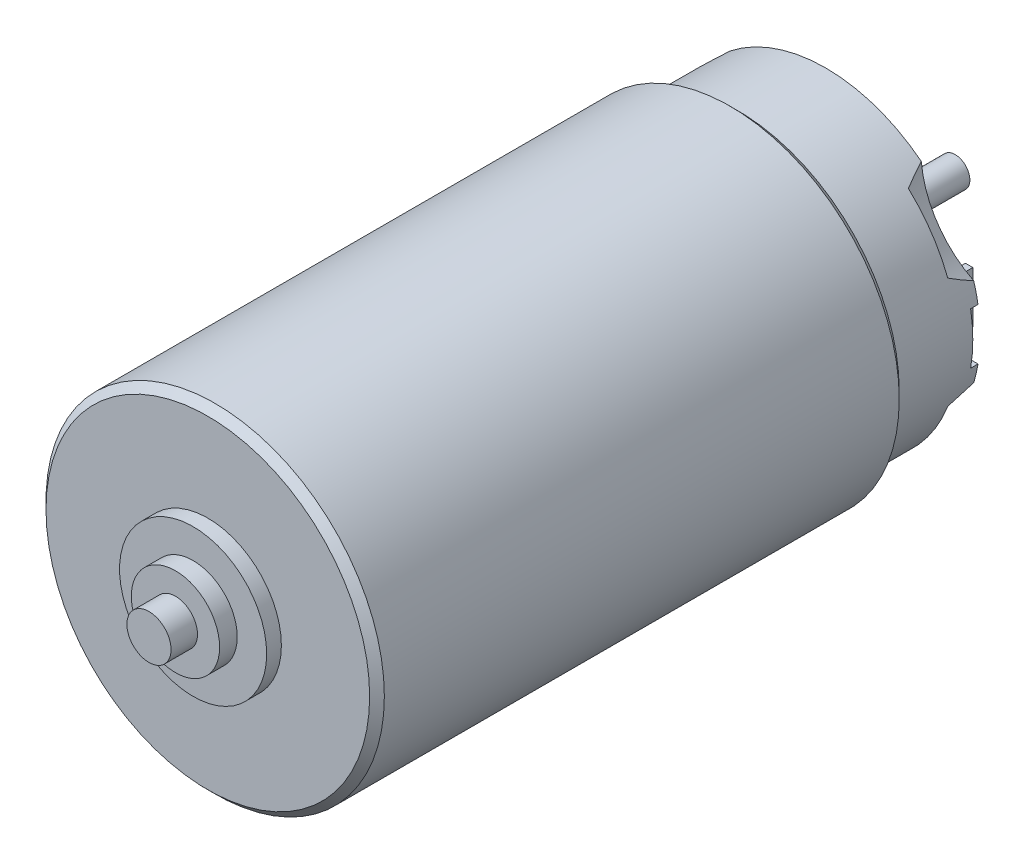
SolidWorks part; units mm, degrees
note: The reader was unsure of these and kept them because the rebuilt part matched: shared geometry of "Croquis1<4>", "Croquis1<5>", "Croquis1<6>", "Croquis3<6>", "Croquis3<8>", "Croquis3<9>".
ref_plane "Alzado" through (0, 0, 0) normal (0, 0, 1) x (1, 0, 0)
ref_plane "Planta" through (0, 0, 0) normal (0, 1, 0) x (1, 0, 0)
ref_plane "Vista lateral" through (0, 0, 0) normal (1, 0, 0) x (0, 0, -1)
sketch "Croquis1" plane through (0, 0, 0) normal (0, 0, 1) x (1, 0, 0)
  circle A0 centre (0, 0) radius 11.5
  circle A1 centre (0, 0) radius 5
  circle A2 centre (0, 0) radius 3
  circle A3 centre (0, 0) radius 1.5
  dimension "D1" = 23
  dimension "D2" = 10
  dimension "D3" = 6
  dimension "D4" = 3
extrude "Saliente-Extruir1" add sketch "Croquis1" against normal blind 36 contours A0
extrude "Saliente-Extruir2" add sketch "Croquis1<4>" along normal blind 1 contours A1
sketch "Croquis1<4>" plane through (0, 0, 0) normal (0, 0, 1) x (1, 0, 0) same geometry as "Croquis1"
extrude "Saliente-Extruir3" add sketch "Croquis1<5>" along normal blind 2.2 contours A2
sketch "Croquis1<5>" plane through (0, 0, 0) normal (0, 0, 1) x (1, 0, 0) same geometry as "Croquis1"
extrude "Saliente-Extruir4" add sketch "Croquis1<6>" along normal blind 4 contours A3
sketch "Croquis1<6>" plane through (0, 0, 0) normal (0, 0, 1) x (1, 0, 0) same geometry as "Croquis1"
sketch "Croquis3" plane through (0, 0, -36) normal (0, 0, -1) x (-1, 0, 0)
  circle A0 centre (0, 0) radius 10.5
  circle A1 centre (0, 0) radius 4.5
  circle A2 centre (0, 0) radius 3
  circle A3 centre (0, 0) radius 1
  dimension "D1" = 21
  dimension "D2" = 9
  dimension "D3" = 6
  dimension "D4" = 2
extrude "Saliente-Extruir5" add sketch "Croquis3" along normal blind 5 contours A0
sketch "Croquis7" plane through (0, 0, -41) normal (0, 0, -1) x (-1, 0, 0)
  circle A0 centre (0, 0) radius 10.5
extrude "Saliente-Extruir10" add sketch "Croquis7" along normal blind 1 separate body
extrude "Saliente-Extruir7" add sketch "Croquis3<6>" along normal blind 14.8 contours A3
sketch "Croquis3<6>" plane through (0, 0, -36) normal (0, 0, -1) x (-1, 0, 0) same geometry as "Croquis3"
extrude "Saliente-Extruir8" add sketch "Croquis3<8>" along normal offset from surface (9.1 mm away) 5.7 contours A2 up to face at (-1, 0, -50.8)
sketch "Croquis3<8>" plane through (0, 0, -36) normal (0, 0, -1) x (-1, 0, 0) same geometry as "Croquis3"
extrude "Saliente-Extruir9" add sketch "Croquis3<9>" along normal blind 7.5 contours A1
sketch "Croquis3<9>" plane through (0, 0, -36) normal (0, 0, -1) x (-1, 0, 0) same geometry as "Croquis3"
sketch "Croquis5" plane through (0, 0, 0) normal (1, 0, 0) x (0, 0, -1)
  line L0 (43.5, -3) -> (43.5, 3) construction
  line L1 (43.5, 3) -> (44.05, 3)
  line L2 (43.5, 3) -> (43.5, 2.4)
  line L3 (43.5, 2.4) -> (44.05, 2.4)
  line L4 (44.05, 3) -> (44.05, 2.4)
  line L6 (0, 0) -> (50.8, 0) construction
  line L7 (0, 5) -> (0, -5) construction
  line L8 (50.8, -1) -> (50.8, 1) construction
  dimension "D1" = 0.6
  dimension "D2" = 0.55
sweep "Cortar-Barrer1" cut profiles "Croquis5" path edge at (-3, 0, -45.1)
sketch "Croquis8" plane through (0, 0, -42) normal (0, 0, -1) x (-1, 0, 0)
  line L0 (10.5, 0) -> (-10.5, 0) construction
  line L1 (0, -10.5) -> (0, 10.5) construction
  line L2 (-10.0623, -3) -> (-10.0623, 0) construction
  line L3 (-6.5, -8.2462) -> (0, -8.2462) construction
  circle A0 centre (0, 0) radius 10.5 construction
  circle A1 centre (0, 0) radius 10.5 construction
  arc A11 (-6.51, -9.48) -> (-11.2128, -2.5542) centre (-12.9754, -8.8106) ccw
  circle A12 centre (0, 0) radius 11.5 construction
  arc A13 (-6.51, -9.48) -> (-11.2128, -2.5542) centre (0, 0) cw
  arc A14 (-6.51, 9.48) -> (-11.2128, 2.5542) centre (-12.9754, 8.8106) cw
  arc A15 (-6.51, 9.48) -> (-11.2128, 2.5542) centre (0, 0) ccw
  arc A16 (6.51, 9.48) -> (11.2128, 2.5542) centre (0, 0) cw
  arc A17 (6.51, 9.48) -> (11.2128, 2.5542) centre (12.9754, 8.8106) ccw
  arc A18 (6.51, -9.48) -> (11.2128, -2.5542) centre (12.9754, -8.8106) cw
  arc A19 (6.51, -9.48) -> (11.2128, -2.5542) centre (0, 0) ccw
  dimension "D3" = 6.5
  dimension "D2" = 3
  dimension "D1" = 6.5
extrude "Cortar-Extruir1" cut sketch "Croquis8" against normal blind 1.5 draft 20
chamfer "Chaflán1" distance 0.5 angle 45 2 edges at (11.5, 0, -36) (11.5, 0, 0)
sketch "Croquis9" plane through (0, 0, -42) normal (0, 0, -1) x (-1, 0, 0)
  line L0 (-8, -1.75) -> (-7.5, -1.75)
  line L1 (-10.5, -1.75) -> (-8, -1.75)
  line L2 (-10.5, -1.75) -> (-10.5, 1.75)
  line L3 (-10.5, 1.75) -> (-8, 1.75)
  line L4 (-8, -1.75) -> (-8, 1.75) construction
  line L5 (-7.5, -1.75) -> (-7.5, 1.75)
  line L6 (-7.5, 1.75) -> (-8, 1.75)
  line L7 (-7.5, -1.75) -> (-8, -1.75)
  line L8 (0, 0) -> (0, -10.5) construction
  line L9 (8, -1.75) -> (7.5, -1.75)
  line L10 (7.5, -1.75) -> (7.5, 1.75)
  line L11 (7.5, 1.75) -> (8, 1.75)
  line L12 (10.5, 1.75) -> (8, 1.75)
  line L13 (10.5, -1.75) -> (10.5, 1.75)
  line L14 (10.5, -1.75) -> (8, -1.75)
  circle A0 centre (0, 0) radius 10.5 construction
  arc A1 (-6.5, -8.2462) -> (6.5, -8.2462) centre (0, 0) ccw construction
  point P4 (-10.5, 0)
  arc M7 (-10.0623, 3) -> (-10.0623, -3) centre (0, 0) ccw
  arc M11 (10.0623, -3) -> (10.0623, 3) centre (0, 0) ccw
  dimension "D1" = 3.5
  dimension "D2" = 8
  dimension "D3" = 0.5
extrude "Cortar-Extruir2" cut sketch "Croquis9" against normal blind 0.5 contours L5 L6 L3 L1 L0 M7 | L14 L12 L11 L10 L9 M11
sketch "Croquis10" plane through (0, 0, -41.5) normal (0, 0, -1) x (-1, 0, 0)
  line L5 (10.3531, 1.75) -> (7.5, 1.75) construction
  line L6 (7.5, -1.75) -> (8, -1.75)
  line L7 (7.5, -1.75) -> (7.5, 1.75)
  line L8 (7.5, 1.75) -> (8, 1.75)
  line L9 (8, -1.75) -> (8, 1.75)
  line L10 (-7.5, 1.75) -> (-10.3531, 1.75) construction
  line L11 (-7.5, -1.75) -> (-8, -1.75)
  line L12 (-7.5, -1.75) -> (-7.5, 1.75)
  line L13 (-7.5, 1.75) -> (-8, 1.75)
  line L14 (-8, -1.75) -> (-8, 1.75)
  dimension "D1" = 0.5
extrude "Saliente-Extruir11" add sketch "Croquis10" along normal blind 2.5
